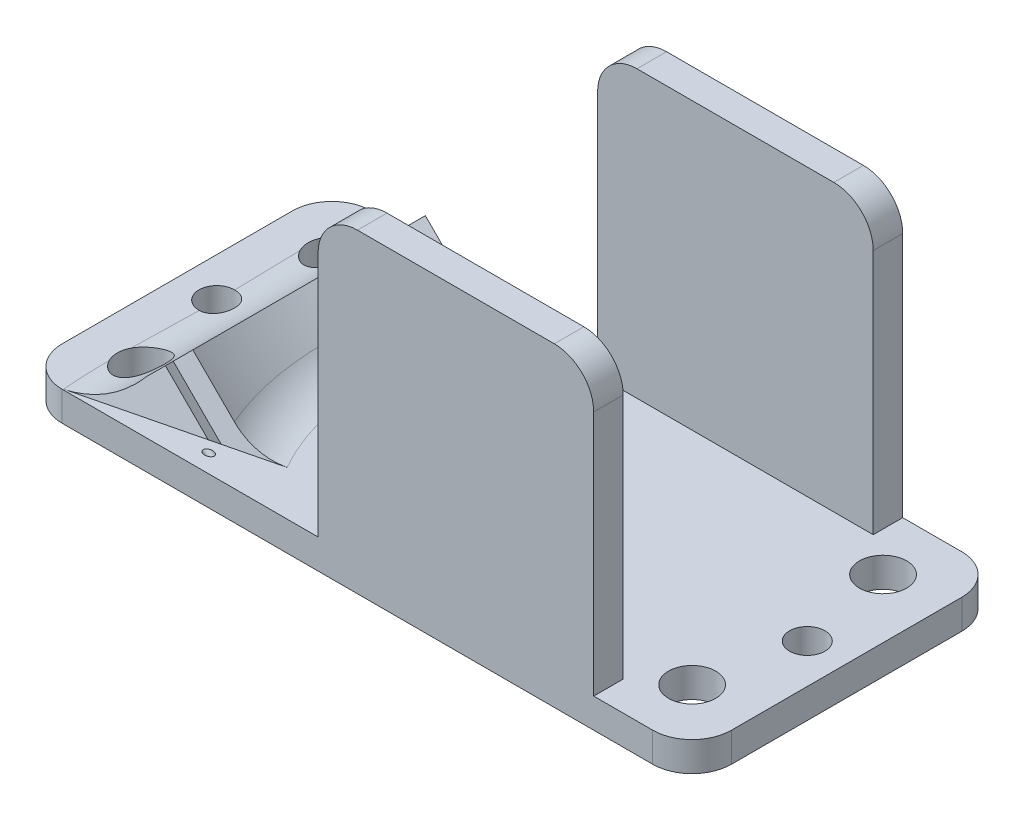
SolidWorks part; units mm, degrees
note: The reader was unsure of these and kept them because the rebuilt part matched: shared geometry of "Sketch17<2>".
ref_plane "Front Plane" through (0, 0, 0) normal (0, 0, 1) x (1, 0, 0)
ref_plane "Top Plane" through (0, 0, 0) normal (0, 1, 0) x (1, 0, 0)
ref_plane "Right Plane" through (0, 0, 0) normal (1, 0, 0) x (0, 0, -1)
sketch "Sketch2" plane through (0, 0, 0) normal (0, 1, 0) x (1, 0, 0)
  line L0 (0, -17) -> (0, 17)
  line L21 (0, -47.4) -> (0, 0) construction
  line L22 (0, 0) -> (0, 47.4) construction
  line L24 (-17, 17) -> (17, 17)
  line L25 (-17, 17) -> (-17, -17)
  line L26 (-17, -17) -> (17, -17)
  line L27 (17, 17) -> (17, -17)
  point P2 (0, 0)
  point P22 (0, 0)
  dimension "D4" = 34
extrude "Boss-Extrude1" add sketch "Sketch2" along normal blind 1.5 contours L24 L27 L26 L25
sketch "Sketch3" plane through (0, 1.5, 0) normal (0, 1, 0) x (1, 0, 0)
  line L0 (-12, 17) -> (-12, -17) construction
  line L1 (-17, 17) -> (17, 17) construction
  line L2 (-17, -17) -> (17, -17) construction
  line L3 (-17, 17) -> (-17, -17) construction
  point P8 (-12, 0)
  dimension "D1" = 5
sketch "Sketch12" [suppressed] plane through (0, 2, 0) normal (0, 1, 0) x (1, 0, 0)
  line L0 (19.0856, 0) -> (-6.6753, 15) construction
  line L1 (19.0856, 0) -> (-6.6753, -15) construction
  line L2 (-1.7286, 12.1196) -> (-5, 0) construction
  line L3 (-5, 0) -> (-1.7286, -12.1196) construction
  line L4 (-15, 15) -> (15, 15) construction
  line L5 (-15, -15) -> (15, -15) construction
  line L9 (-15, 15) -> (-15, -15) construction
  line L10 (15, 15) -> (15, -15) construction
  line L11 (-15, 0) -> (15, 0) construction
  line L12 (-0.8644, 11.6164) -> (-1.7286, 12.1196)
  line L13 (-2.5188, 12.5797) -> (-3.383, 13.0829)
  line L14 (-0.8644, -11.6164) -> (-1.7286, -12.1196)
  line L15 (-2.5188, -12.5797) -> (-3.383, -13.0829)
  arc A0 (-0.8644, 11.6164) -> (-0.8644, -11.6164) centre (19.0856, 0) ccw
  arc A1 (-3.383, 13.0829) -> (-3.383, -13.0829) centre (19.0856, 0) ccw
  arc A2 (-2.5188, -12.5797) -> (-2.5188, 12.5797) centre (19.0856, 0) cw
  arc A3 (-1.7286, -12.1196) -> (-1.7286, 12.1196) centre (19.0856, 0) cw
  point P11 (-5, 0)
  point P29 (-15, 0)
  point P30 (15, 0)
  dimension "D1" = 19.05
  dimension "D3" = 1
  dimension "D4" = 1
  dimension "D5" = 0.4
  dimension "D2" = 12.7
ref_plane "Plane1" [suppressed] through (0, 0, 0) normal (0, 0, 1) x (1, 0, 0)
sketch "Sketch13" [suppressed] plane through (0, 0, 0) normal (0, 0, 1) x (1, 0, 0)
  line L0 (-5, 2) -> (-15, 12)
  line L1 (-15, 2) -> (15, 2) construction
  dimension "D1" = 45
  dimension "D2" = 10
ref_plane "Plane2" through (-6.75, 6.75, 0) normal (-0.7071, 0.7071, 0) x (0, 0, 1)
sketch "Sketch14" plane through (-6.75, 6.75, 0) normal (-0.7071, 0.7071, 0) x (0, 0, 1)
  line L0 (-1.0634, 9.9543) -> (-15.2099, -30.9016) construction
  line L1 (-0.1309, 13.4034) -> (14.0156, -27.4525) construction
  line L2 (-6.3639, -5.354) -> (0, -7.4246) construction
  line L3 (0, -7.4246) -> (6.3639, -5.354) construction
  line L4 (0, 13.0254) -> (0, -7.4246) construction
  line L5 (-17, -7.4246) -> (17, -7.4246) construction
  line L6 (5.9059, -4.0311) -> (6.2331, -4.9761)
  line L7 (6.3639, -5.354) -> (6.6911, -6.299)
  line L8 (-6.6911, -6.299) -> (-6.3639, -5.354)
  line L9 (-6.2331, -4.9761) -> (-5.9059, -4.0311)
  arc A1 (-6.6911, -6.299) -> (6.6911, -6.299) centre (0, 13.0254) ccw
  arc A2 (-6.2331, -4.9761) -> (6.2331, -4.9761) centre (0, 13.0254) ccw
  arc A3 (5.9059, -4.0311) -> (-5.9059, -4.0311) centre (0, 13.0254) cw
  arc A4 (-6.2331, -4.9761) -> (6.2331, -4.9761) centre (0, 13.0254) ccw
  arc A5 (6.3639, -5.354) -> (-6.3639, -5.354) centre (0, 13.0254) cw
  point P8 (0, -7.4246)
  point P14 (6.3639, -5.354)
  point P17 (-6.3639, -5.354)
  point P18 (0, -7.4246)
  point P24 (-6.2331, -4.9761)
  dimension "D3" = 1
  dimension "D4" = 1
  dimension "D2" = 12.7
  dimension "D5" = 19.05
  dimension "D1" = 0.4
  dimension "D6" = 90
extrude "Boss-Extrude2" add sketch "Sketch14" along normal blind 1 and the other way blind 9 contours A5 L8 A1 L7 | L6 A4 L9 A3
sketch "Sketch17" plane through (-6.75, 6.75, 0) normal (-0.7071, 0.7071, 0) x (0, 0, 1)
  line L0 (-6.3639, -5.354) -> (-6.2331, -4.9761)
  line L1 (6.2331, -4.9761) -> (6.3639, -5.354)
  arc A0 (-6.2331, -4.9761) -> (6.2331, -4.9761) centre (0, 13.0254) ccw
  arc A1 (-6.3639, -5.354) -> (6.3639, -5.354) centre (0, 13.0254) ccw
extrude "Boss-Extrude3" add sketch "Sketch17<2>" against normal blind 15
sketch "Sketch17<2>" plane through (-6.75, 6.75, 0) normal (-0.7071, 0.7071, 0) x (0, 0, 1) same geometry as "Sketch17"
extrude "Cut-Extrude1" cut sketch "Sketch17" against normal blind 2.75
sketch "Sketch19" plane through (-6.75, 6.75, 0) normal (-0.7071, 0.7071, 0) x (0, 0, 1)
  line L0 (-7, -5.1213) -> (-6.856, -4.7481) construction
  line L1 (0, -6.0246) -> (0, -6.4246) construction
  line L2 (6.856, -4.7481) -> (7, -5.1213) construction
  arc A0 (-6.2331, -4.9761) -> (6.2331, -4.9761) centre (0, 13.0254) ccw construction
  arc A1 (-6.3639, -5.354) -> (6.3639, -5.354) centre (0, 13.0254) ccw construction
  circle A2 centre (-6.928, -4.9347) radius 0.2
  circle A3 centre (0, -6.2246) radius 0.2
  circle A4 centre (6.928, -4.9347) radius 0.2
  point P0 (-6.856, -4.7481)
  point P1 (0, -6.0246)
  point P5 (-7, -5.1213)
  point P6 (0, -6.4246)
  point P7 (6.856, -4.7481)
  point P8 (7, -5.1213)
  dimension "D1" = 0.4
  dimension "D2" = 7
  dimension "D3" = 7
extrude "Cut-Extrude4" cut sketch "Sketch19" against normal blind 7
sketch "Sketch20" plane through (17, 0, 0) normal (1, 0, 0) x (0, 0, -1)
  line L1 (-17, 0) -> (17, 0)
  line L2 (-17, 0) -> (-17, -20)
  line L3 (-17, -20) -> (17, -20)
  line L4 (17, 0) -> (17, -20)
  dimension "D1" = 20
extrude "Cut-Extrude5" cut sketch "Sketch20" against normal through all
fillet "Fillet2" radius 3 1 edges at (-8.6059, 1.5, 0)
sketch "Sketch26" plane through (0, 1.5, 0) normal (0, 1, 0) x (1, 0, 0)
  line L0 (-17, 0) -> (0, -17)
  line L1 (-17, 17) -> (-17, -17) construction
  line L2 (0, -17) -> (4.2426, -12.7574)
  line L3 (4.2426, -12.7574) -> (11, -19.5147)
  line L4 (11, -19.5147) -> (11, 19.5147) construction
  line L5 (11, 19.5147) -> (4.2426, 12.7574)
  line L6 (4.2426, 12.7574) -> (0, 17)
  line L7 (0, 17) -> (-17, 0)
  line L8 (-17, 17) -> (17, 17) construction
  line L9 (-17, -17) -> (17, -17) construction
  line L10 (17, 17) -> (17, -17) construction
  line L11 (11, 7.85) -> (17, 7.85)
  line L12 (11, 7.85) -> (11, -7.85) construction
  line L13 (11, -7.85) -> (17, -7.85)
  line L14 (17, 7.85) -> (17, -7.85)
  line L15 (11, 19.5147) -> (11, 7.85)
  line L16 (11, -7.85) -> (11, -19.5147)
  point P17 (11, 0)
  point P18 (11, 0)
  dimension "D1" = 15.7
  dimension "D2" = 28
  dimension "D3" = 6
extrude "Cut-Extrude8" [suppressed] cut sketch "Sketch26" against normal through all both and the other way through all flip side to cut
sketch "Sketch27" [suppressed] plane through (0, 2, 0) normal (0, 1, 0) x (1, 0, 0)
  line L0 (-2.1213, 27.8787) -> (2.1213, 23.636) construction
  line L1 (0, 30) -> (-14.0968, 15.9032) construction
  line L2 (-2, 19.5147) -> (4.2426, 25.7574) construction
  line L3 (0, 25.7574) -> (2.1213, 27.8787) construction
  line L4 (4.2426, 25.7574) -> (0, 30) construction
  line L5 (2.1213, -23.636) -> (-2.1213, -27.8787) construction
  line L6 (4.2426, -25.7574) -> (-2, -19.5147) construction
  line L7 (-14.0968, -15.9032) -> (0, -30) construction
  line L8 (0, -25.7574) -> (2.1213, -27.8787) construction
  line L9 (0, -30) -> (4.2426, -25.7574) construction
  point P0 (0, 25.7574)
  point P1 (0, -25.7574)
  dimension "D1" = 3
  dimension "D2" = 3
hole_wizard "M2 Clearance Hole1" [suppressed] positions "Sketch28" profile "Sketch29" hole size "M2" standard "ISO"
sketch "Sketch28" [suppressed] plane through (0, 2, 0) normal (0, 1, 0) x (1, 0, 0)
  point P0 (0, 25.7574)
  point P3 (0, -25.7574)
sketch "Sketch29" plane through (0, 2, -25.7574) normal (1, 0, 0) x (0, 0, 1)
  line L0 (0, 0) -> (0, 2)
  line L1 (0, 2) -> (1.1, 2)
  line L2 (1.1, 2) -> (1.1, 0)
  line L5 (1.1, 0) -> (0, 0)
  line L11 (0, -6.35) -> (0, 107.95) construction
  dimension "Thru Hole Dia." = 2.2
  dimension "Thru Hole Depth" = 2
fillet "Fillet3" [suppressed] radius 4
fillet "Fillet4" [suppressed] radius 3
sketch "Sketch30" plane through (0, 1.5, 0) normal (0, 1, 0) x (1, 0, 0)
  line L0 (-17, 17) -> (-17, -17) construction
  line L1 (-17, 7.85) -> (17, 7.85)
  line L2 (-17, 7.85) -> (-17, -7.85)
  line L3 (-17, -7.85) -> (17, -7.85)
  line L4 (17, 7.85) -> (17, -7.85)
  line L5 (17, 17) -> (17, -17) construction
  point P8 (-17, 0)
  point P9 (-17, 0)
  dimension "D1" = 15.7
extrude "Cut-Extrude9" cut sketch "Sketch30" against normal through all and the other way through all flip side to cut
sketch "Sketch31" plane through (0, 1.5, 0) normal (0, 1, 0) x (1, 0, 0)
  line L1 (12, 7.85) -> (-2, 7.85)
  line L2 (12, 7.85) -> (12, 6.35)
  line L3 (12, 6.35) -> (-2, 6.35)
  line L4 (-2, 7.85) -> (-2, 6.35)
  line L5 (-17, -7.85) -> (17, -7.85) construction
  line L6 (12, -7.85) -> (-2, -7.85)
  line L7 (12, -7.85) -> (12, -6.35)
  line L8 (12, -6.35) -> (-2, -6.35)
  line L9 (-2, -7.85) -> (-2, -6.35)
  line L11 (-17, 7.85) -> (-17, -7.85) construction
  line L12 (17, 7.85) -> (-17, 7.85) construction
  dimension "D1" = 1.5
  dimension "D3" = 15
  dimension "D2" = 14
extrude "Boss-Extrude4" add sketch "Sketch31" along normal blind 14.5
sketch "Sketch32" plane through (0, 1.5, 0) normal (0, 1, 0) x (1, 0, 0)
  line L0 (-17, 7.85) -> (-17, -7.85) construction
  line L1 (17, 7.85) -> (17, -7.85) construction
  line L2 (12, -7.85) -> (17, -7.85) construction
  line L3 (-8.8, 0) -> (8.8, 0) construction
  point P0 (-14, -4.85)
  point P3 (14, -4.85)
  point P4 (14, -4.85)
  point P17 (-14, 4.85)
  point P18 (14, 4.85)
  dimension "D1" = 3
  dimension "D2" = 3
  dimension "D3" = 3
hole_wizard "M2 Clearance Hole2" positions "Sketch33" profile "Sketch34" hole size "M2" standard "ANSI Metric" end condition through all
sketch "Sketch33" plane through (0, 1.5, 0) normal (0, 1, 0) x (1, 0, 0)
  point P0 (-14, 4.85)
  point P3 (-14, -4.85)
  point P6 (14, -4.85)
  point P9 (14, 4.85)
sketch "Sketch34" plane through (-14, 1.5, -4.85) normal (1, 0, 0) x (0, 0, 1)
  line L0 (0, 0) -> (0, 1.5)
  line L1 (0, 1.5) -> (1.2, 1.5)
  line L2 (1.2, 1.5) -> (1.2, 0)
  line L5 (1.2, 0) -> (0, 0)
  line L11 (0, -6.35) -> (0, 107.95) construction
  dimension "Thru Hole Dia." = 2.4
  dimension "Thru Hole Depth" = 1.5
sketch "Sketch37" [suppressed] plane through (0, 2, 0) normal (0, 1, 0) x (1, 0, 0)
  line L1 (25, 12.7) -> (-5, 12.7)
  line L2 (25, 12.7) -> (25, 16.7)
  line L3 (25, 16.7) -> (-5, 16.7)
  line L4 (-5, 12.7) -> (-5, 16.7)
  line L5 (27, 16.7) -> (1, 16.7) construction
  line L10 (30, 13.7) -> (30, -13.7) construction
  line L11 (-8.085, 0) -> (8.085, 0) construction
  line L12 (25, -16.7) -> (-5, -16.7)
  line L13 (-5, -12.7) -> (-5, -16.7)
  line L14 (25, -12.7) -> (-5, -12.7)
  line L15 (25, -12.7) -> (25, -16.7)
  dimension "D1" = 5
  dimension "D2" = 1.5
  dimension "D3" = 30
sketch "Sketch38" plane through (0, 1.5, 0) normal (0, 1, 0) x (1, 0, 0)
  line L0 (17, 0) -> (-17, 0) construction
  line L1 (17, 7.85) -> (17, -7.85) construction
  line L2 (-17, 7.85) -> (-17, -7.85) construction
  point P6 (15, 0)
  point P7 (-15, 0)
  dimension "D1" = 2
  dimension "D2" = 2
hole_wizard "M1.6 Clearance Hole1" positions "Sketch39" profile "Sketch40" hole size "M1.6" standard "ANSI Metric" end condition through all
sketch "Sketch39" plane through (0, 1.5, 0) normal (0, 1, 0) x (1, 0, 0)
  point P0 (15, 0)
  point P3 (-15, 0)
sketch "Sketch40" plane through (15, 1.5, 0) normal (1, 0, 0) x (0, 0, 1)
  line L0 (0, 0) -> (0, 1.5)
  line L1 (0, 1.5) -> (0.9, 1.5)
  line L2 (0.9, 1.5) -> (0.9, 0)
  line L5 (0.9, 0) -> (0, 0)
  line L11 (0, -6.35) -> (0, 107.95) construction
  dimension "Thru Hole Dia." = 1.8
  dimension "Thru Hole Depth" = 1.5
fillet "Fillet1" radius 4 1 edges at (-12, 1.5, 0)
extrude "Boss-Extrude5" [suppressed] add sketch "Sketch37" along normal blind 14.5
fillet "Fillet5" radius 2 8 edges at (-17, 0.75, 7.85) (-17, 0.75, -7.85) (12, 16, -7.1) (-2, 16, 7.1) (-2, 16, -7.1) (12, 16, 7.1) (17, 0.75, 7.85) (17, 0.75, -7.85)
equation "\"mountWallThickness\"= 1.00mm'Thickness of the holder wall."
equation "\"arcLength\"= 0.5in'Basically the width of the tape spring when flat."
equation "\"tapeSpringThickness\"= 0.4mm'Measure experimentally."
equation "\"curvatureRadius\" = 0.75in'Outer radius of the mandrel for the tape spring."
equation "\"distanceBetweenWires\"= 7mm'(horizontal) distance between wires; should be pretty close to the flat distanct."
equation "\"D1@Sketch12\"=\"curvatureRadius\""
equation "\"D2@Sketch12\"=\"arcLength\""
equation "\"D3@Sketch12\"=\"mountWallThickness\""
equation "\"D4@Sketch12\"=\"mountWallThickness\""
equation "\"D5@Sketch12\"=\"tapeSpringThickness\""
equation "\"D3@Sketch14\"=\"mountWallThickness\""
equation "\"D1@Sketch14\"=\"tapeSpringThickness\""
equation "\"D4@Sketch14\"=\"mountWallThickness\""
equation "\"D1@Sketch19\"=\"tapeSpringThickness\""
equation "\"mountWallLength\"= 1mm'Total length of the holding walls."
equation "\"D1@Boss-Extrude2\"=\"mountWallLength\""
equation "\"mountWallPlacement\"= 5mm'Distance from the edge of the plate to the base of the mount wall (minus the fillet)."
equation "\"D1@Sketch3\"=\"mountWallPlacement\""
equation "\"D2@Sketch14\"=\"arcLength\""
equation "\"D5@Sketch14\"=\"curvatureRadius\""
equation "\"retainingWallThickness\"= 1.5mm'Thickness of the antenna retaining wall, the wall that prevents the antenna from deploying sideways while stowed."
equation "\"D1@Sketch30\"=(\"arcLength\"+\"retainingWallThickness\"*2)"
equation "\"retainingWallHeight\"= 14.5mm'How high the retaining walls are."
equation "\"D1@Sketch31\"=\"retainingWallThickness\""
equation "\"D1@Boss-Extrude4\"=\"retainingWallHeight\""
equation "\"D1@Sketch26\"=\"arcLength\"+\"retainingWallThickness\"*2"
equation "\"D2@Sketch37\"=\"retainingWallThickness\""
equation "\"D1@Boss-Extrude5\"=\"retainingWallHeight\""
